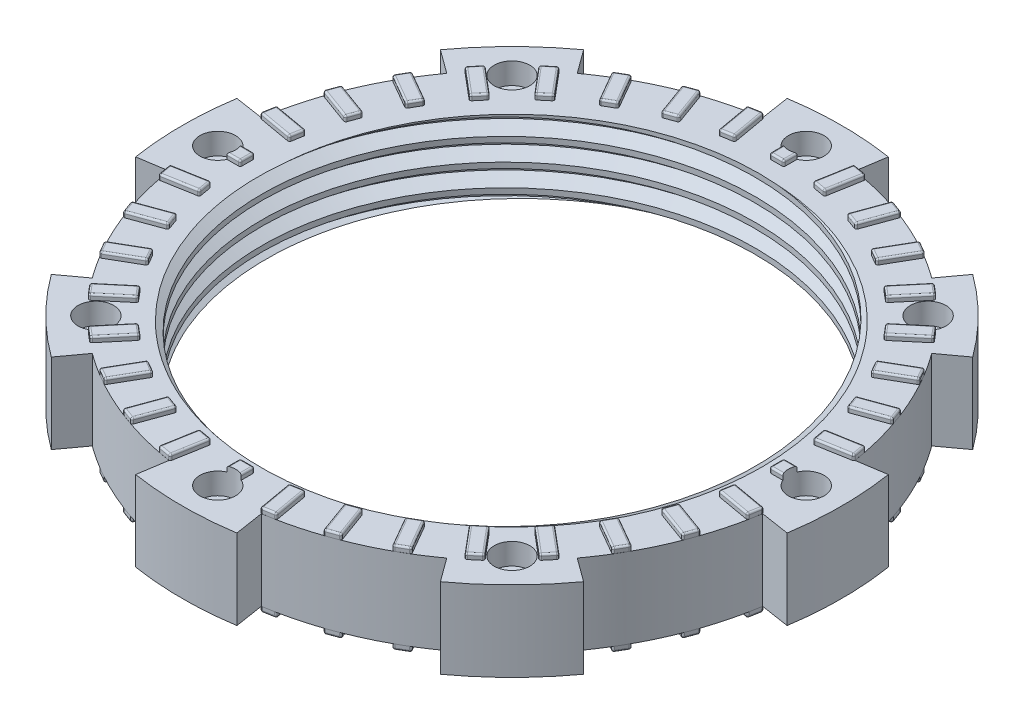
SolidWorks part; units mm, degrees
material "ABS"
ref_plane "Front" through (0, 0, 0) normal (0, 0, 1) x (1, 0, 0)
ref_plane "Top" through (0, 0, 0) normal (0, 1, 0) x (1, 0, 0)
ref_plane "Side" through (0, 0, 0) normal (1, 0, 0) x (0, 0, -1)
sketch "Sketch1" plane through (0, 0, 0) normal (0, 1, 0) x (1, 0, 0)
  circle A0 centre (0, 0) radius 14.525
  circle A1 centre (0, 0) radius 16.855
  dimension "D1" = 29.05
  dimension "D2" = 33.71
extrude "Boss-Extrude1" add sketch "Sketch1" along normal mid plane 4.5
thread "Thread1" pitch 1.25 method extrude profile "Thread Profile2" start angle 0, offset 1.5, length 10, pitch 1.25, diameter 29.05
ref_plane "Plane2" through (14.525, -3.75, 0) normal (0, 0, 1) x (1, 0, 0)
sketch "Thread Profile2" plane through (14.525, -3.75, 0) normal (0, 0, 1) x (1, 0, 0)
  line L0 (0, 0) -> (0, 1.25) construction
  line L11 (0, 0) -> (0, 1.0937)
  line L12 (0, 1.0937) -> (-0.6766, 0.7031)
  line L13 (-0.6766, 0.7031) -> (-0.6766, 0.3906)
  line L15 (-0.6766, 0.3906) -> (0, 0)
  line L17 (-0.6766, 0.5469) -> (0, 0.5469) construction
  point P2 (0, 0)
  dimension "Pitch" = 1.25
  dimension "Profile_Angle" = 60
  dimension "Profile_Land" = 0.3125
  dimension "Profile_Height" = 0.6766
sketch "Sketch12" plane through (0, 0, 0) normal (1, 0, 0) x (0, 0, -1)
  line L1 (16.855, 2.25) -> (-17.3838, 2.25)
  line L2 (16.855, 2.25) -> (16.855, 10.5382)
  line L3 (16.855, 10.5382) -> (-17.3838, 10.5382)
  line L4 (-17.3838, 2.25) -> (-17.3838, 10.5382)
extrude "Cut-Extrude3" cut sketch "Sketch12" against normal through all both and the other way through all
mirror "Mirror4" about plane through (0, 0, 0) normal (0, 1, 0) of "Cut-Extrude3"
sketch "Sketch2" plane through (0, 2.25, 0) normal (0, 1, 0) x (1, 0, 0)
  line L0 (-2.5796, 16.5953) -> (-2.8415, 18.2805)
  line L5 (0, 18.5) -> (0, 16.7946)
  line L6 (0, 16.7946) -> (0, 0) construction
  line L7 (0, 0) -> (-2.5796, 16.5953) construction
  circle A3 centre (0, 0) radius 18.5 construction
  circle A4 centre (0, 0) radius 16.7946 construction
  arc A5 (-2.8415, 18.2805) -> (0, 18.5) centre (0, 0) cw
  arc A6 (0, 16.7946) -> (-2.5796, 16.5953) centre (0, 0) ccw
  dimension "D1" = 37
  dimension "D2" = 2.85
extrude "Boss-Extrude2" add sketch "Sketch2" against normal up to surface (4.5 mm away) up to face at (0, -2.25, 16.855)
mirror "Mirror1" about plane through (0, 0, 0) normal (1, 0, 0) of "Boss-Extrude2"
sketch "Sketch3" plane through (0, 2.25, 0) normal (0, 1, 0) x (1, 0, 0)
  line L1 (-0.4, 14.8503) -> (0.4, 14.8503)
  line L2 (-0.4, 14.8503) -> (-0.4, 16.8503)
  line L3 (-0.4, 16.8503) -> (0.4, 16.8503)
  line L4 (0.4, 14.8503) -> (0.4, 16.8503)
  line L5 (-0.4, 14.8503) -> (0.4, 16.8503) construction
  line L6 (-0.4, 16.8503) -> (0.4, 14.8503) construction
  circle A0 centre (0, 0) radius 16.855 construction
  point P4 (0, 15.8503)
  point P9 (0, 0)
  dimension "D1" = 0.8
  dimension "D2" = 2
extrude "Boss-Extrude3" add sketch "Sketch3" along normal blind 0.3 separate body
fillet "Fillet1" radius 0.1 8 edges at (0, 2.55, -14.8503) (-0.4, 2.55, -15.8503) (0, 2.55, -16.8503) (0.4, 2.55, -15.8503) (-0.4, 2.4, -14.8503) (0.4, 2.4, -14.8503) (0.4, 2.4, -16.8503) (-0.4, 2.4, -16.8503)
pattern_circular "CirPattern1" count 36 over 360 about axis through (0, 2.25, 0) along (0, 1, 0) of bodies 108
pattern_circular "CirPattern4" count 8 over 360 about axis through (0, 2.25, 0) along (0, 1, 0) of "Mirror1", "Boss-Extrude2"
mirror "Mirror2" about plane through (0, 0, 0) normal (0, 1, 0) of bodies 109 143 142 141 140 139 138 137 136 135 134 133 132 131 130 129 128 127 126 125 124 123 122 121 120 119 118 117 116 115 114 113 112 111 110 108
combine bodies "Combine1" bodies to combine 115 162 138 156 150 131 124 179 117 173 140 167 110 144 161 133 155 149 126 119 142 178 112 172 135 166 160 128 154 148 121 114 137 177 171 130 165 108 159 123
sketch "Sketch4" plane through (0, 2.55, 0) normal (0, 1, 0) x (1, 0, 0)
  line L0 (0, 14.525) -> (0, 18.5) construction
  circle A0 centre (0, 16.5125) radius 1
  circle A1 centre (0, 0) radius 14.525 construction
  arc A2 (2.8415, 18.2805) -> (-2.8415, 18.2805) centre (0, 0) ccw construction
  point P2 (0, 16.5125)
  dimension "D1" = 2
extrude "Cut-Extrude1" cut sketch "Sketch4" against normal offset from surface (1.5 mm away) 1.2 up to face at (13.7267, 2.25, -7.9251)
pattern_circular "CirPattern5" count 8 over 360 about axis through (0, 2.25, 0) along (0, 1, 0) of "Cut-Extrude1"
sketch "Sketch5" plane through (0, -2.55, 0) normal (0, -1, 0) x (1, 0, 0)
  circle A0 centre (0, -16.5125) radius 1
  arc A1 (-0.4, -15.596) -> (0.4, -15.596) centre (0, -16.5125) ccw construction
extrude "Cut-Extrude2" cut sketch "Sketch5" against normal offset from surface (1.5 mm away) 1.2 up to face at (2.7524, -2.25, 15.6095)
pattern_circular "CirPattern6" count 8 over 360 about axis through (0, -2.25, 0) along (0, 1, 0) of "Cut-Extrude2"
